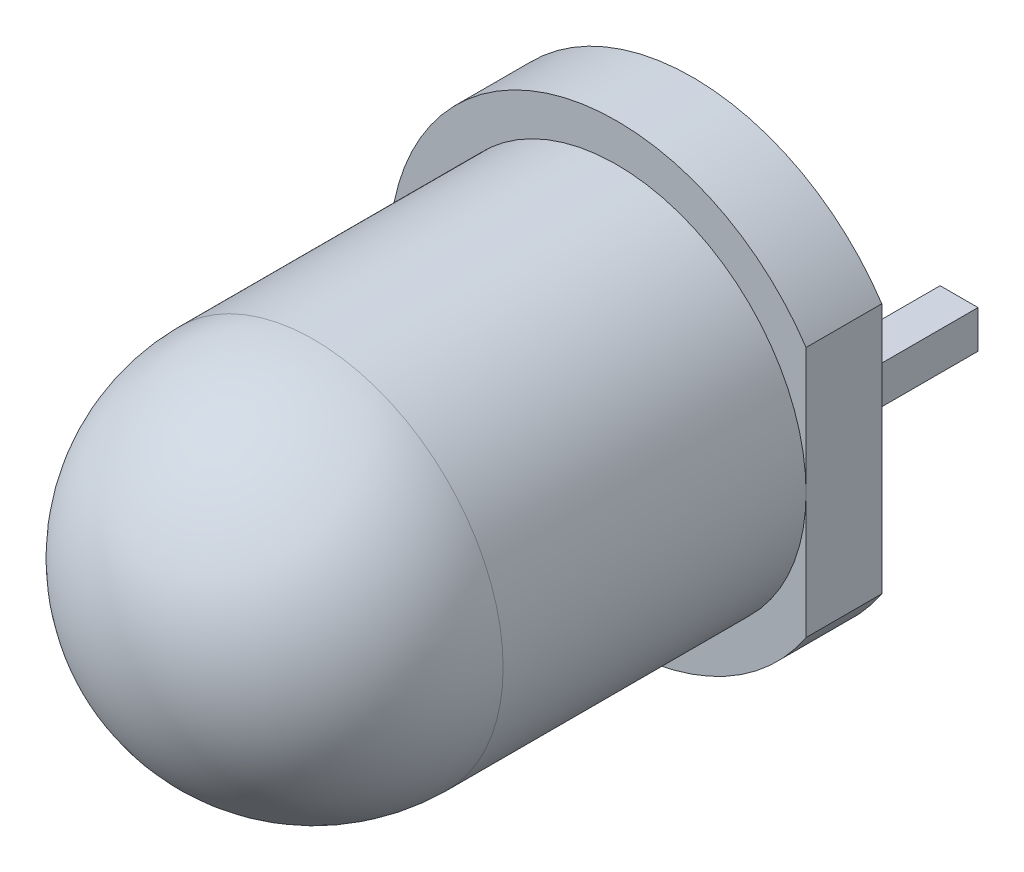
SolidWorks part; units mm, degrees
ref_plane "Front Plane" through (0, 0, 0) normal (0, 0, 1) x (1, 0, 0)
ref_plane "Top Plane" through (0, 0, 0) normal (0, 1, 0) x (1, 0, 0)
ref_plane "Right Plane" through (0, 0, 0) normal (1, 0, 0) x (0, 0, -1)
sketch "Sketch1" plane through (0, 0, 0) normal (0, 0, 1) x (1, 0, 0)
  circle A0 centre (0, 0) radius 3
  dimension "D1" = 6
extrude "Boss-Extrude1" add sketch "Sketch1" along normal blind 1
sketch "Sketch2" plane through (0, 0, 1) normal (0, 0, 1) x (1, 0, 0)
  circle A0 centre (0, 0) radius 2.5
  dimension "D1" = 5
extrude "Boss-Extrude2" add sketch "Sketch2" along normal blind 4
dome "Dome1" faces to dome 1 distance 2.5 reverse direction no elliptical dome no face at (2.5, 0, 5) parameters "D1"=2.5
sketch "Sketch3" plane through (0, 0, 1) normal (0, 0, 1) x (1, 0, 0)
  line L1 (2.5, 1.8503) -> (3, 1.8503)
  line L2 (2.5, 1.8503) -> (2.5, -2.181)
  line L3 (2.5, -2.181) -> (3, -2.181)
  line L4 (3, 1.8503) -> (3, -2.181)
  circle A0 centre (0, 0) radius 3 construction
  circle A1 centre (0, 0) radius 2.5 construction
extrude "Cut-Extrude1" cut sketch "Sketch3" against normal up to next
ref_plane "Plane3" through (0, 0, 0) normal (0, 1, 0) x (1, 0, 0)
sketch "Sketch8" plane through (0, 0, 0) normal (0, 1, 0) x (1, 0, 0)
  line L0 (0, 0) -> (-1.27, 0) construction
  line L1 (2.5, 0) -> (-3, 0) construction
  line L2 (-1.27, 0) -> (-1.27, 2)
  dimension "D1" = 2
  dimension "D2" = 1.27
sheet metal parameters "Sheet-Metal1" thickness 0.5 parameters "D1"=0.1
base flange "Base-Flange1" sketch "Sketch8" end condition mid plane depth 0.5 reverse direction no thickness 0.5 reverse thickness direction no bend radius 0.1
sketch "Sketch9" plane through (0, 0, 0) normal (0, 1, 0) x (1, 0, 0)
  line L0 (1.27, 0) -> (1.27, 2)
  line L1 (-1.27, 2) -> (-0.77, 2) construction
  line L2 (2.5, 0) -> (-3, 0) construction
  dimension "D1" = 1.27
sheet metal parameters "Sheet-Metal2" thickness 0.5 parameters "D1"=0.1
base flange "Base-Flange2" sketch "Sketch9" end condition mid plane depth 0.5 reverse direction no thickness 0.5 reverse thickness direction no bend radius 0.1
sketch "Sketch10" plane through (0, 0, 0) normal (0, 0, -1) x (-1, 0, 0)
  line L0 (0, 0) -> (0, 3) construction
  arc A0 (-2.5, -1.6583) -> (-2.5, 1.6583) centre (0, 0) ccw construction
ref_plane "Plane4" through (0, 0, 0) normal (1, 0, 0) x (0, 0, -1)
ref_axis "Axis1" through (0, 0, 5) along (0, 0, -1)
sketch "Sketch11" plane through (0, 0, -2) normal (0, 0, -1) x (-1, 0, 0)
  line L0 (-1.27, -0.25) -> (-1.77, -0.25) construction
  point P0 (-1.52, 0)
  point P1 (-1.52, -0.25)
flat pattern "Flat-Pattern1" [suppressed]
sketch "Bend-Lines1" plane through (0, 0, 0) normal (0, 1, 0) x (1, 0, 0)
sketch3d "Bounding-Box1" [suppressed]
  line L0 (0, 0.5, 0) -> (4.53, 0.5, 0) construction
  line L1 (0, 0, 0) -> (4.53, 0, 0) construction
  line L2 (0, 0.5, 0) -> (0, 0, 0) construction
  line L3 (4.53, 0.5, 0) -> (4.53, 0, 0) construction
flat pattern "Flat-Pattern2" [suppressed]
sketch "Bend-Lines2" plane through (0, 0, 0) normal (0, 1, 0) x (1, 0, 0)
sketch "Bounding-Box2" [suppressed] plane through (0, 0, 0) normal (0, 1, 0) x (1, 0, 0)
